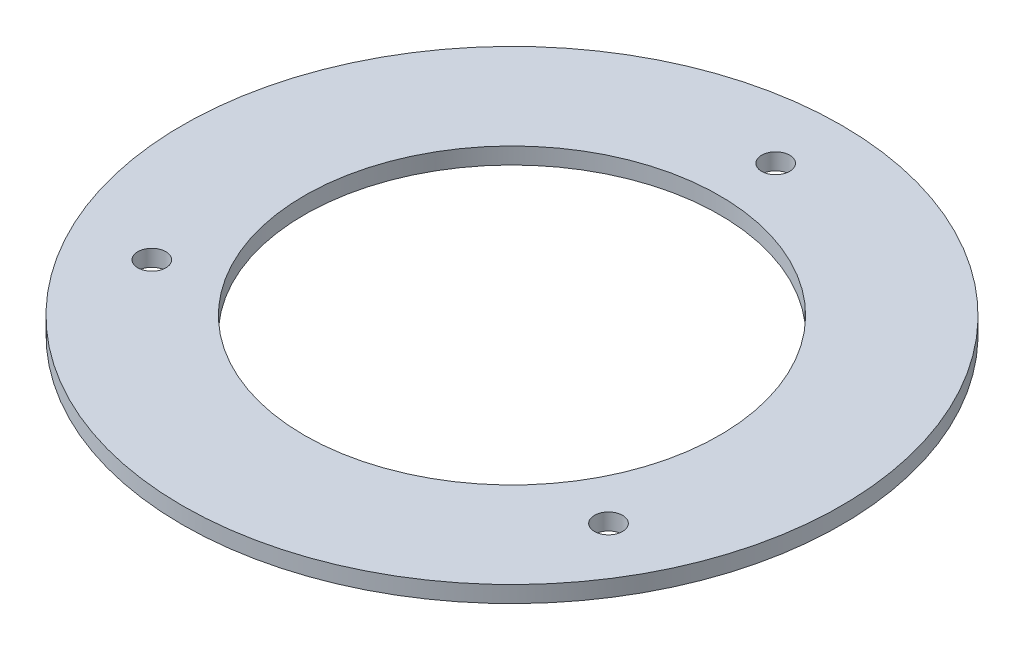
SolidWorks part; units mm, degrees
ref_plane "Front Plane" through (0, 0, 0) normal (0, 0, 1) x (1, 0, 0)
ref_plane "Top Plane" through (0, 0, 0) normal (0, 1, 0) x (1, 0, 0)
ref_plane "Right Plane" through (0, 0, 0) normal (1, 0, 0) x (0, 0, -1)
sketch "Sketch1" plane through (0, 0, 0) normal (0, 1, 0) x (1, 0, 0)
  circle A0 centre (0, 0) radius 63.5
  dimension "D1" = 127
extrude "Boss-Extrude1" add sketch "Sketch1" along normal blind 3.18
sketch "Sketch2" plane through (0, 3.18, 0) normal (0, 1, 0) x (1, 0, 0)
  circle A0 centre (0, 0) radius 40.005
  dimension "D1" = 80.01
extrude "Cut-Extrude1" cut sketch "Sketch2" against normal blind 3.18
ref_axis "Axis2" through (0, 0, 0) along (0, 1, 0)
sketch "Sketch5" plane through (0, 3.18, 0) normal (0, 1, 0) x (1, 0, 0)
  line L0 (0, -64.6358) -> (0, 63.5)
  circle A0 centre (0, 0) radius 63.5 construction
hole_wizard "Hole for #8 300® SC Nuts (SP)1" positions "3DSketch2" profile "Sketch7" hole size "#8-32" standard "PEM® Inch"
sketch3d "3DSketch2"
  line L0 (0, 3.18, 64.6358) -> (0, 3.18, -63.5) construction
  line L1 (0, 0, 0) -> (0, 3.18, 0) construction
  point P0 (0, 3.18, -50.8)
  dimension "D1" = 50.8
sketch "Sketch7" plane through (0, 3.18, -50.8) normal (1, 0, 0) x (0, 0, 1)
  line L0 (0, 0) -> (0, 21.3754)
  line L1 (0, 21.3754) -> (2.7051, 19.75)
  line L2 (2.7051, 19.75) -> (2.7051, 0)
  line L5 (2.7051, 0) -> (0, 0)
  line L10 (0, 21.3754) -> (-2.7051, 19.75) construction
  line L11 (0, -6.35) -> (0, 107.95) construction
  dimension "Hole Dia." = 5.4102
  dimension "Hole Depth" = 19.75
  dimension "Drill Angle" = 118
pattern_circular "CirPattern1" count 3 over 360 about axis through (0, 0, 0) along (0, 1, 0) of "Hole for #8 300® SC Nuts (SP)1"
equation "\"ODia\"= 5in"
equation "\"IDia\"= 3.15in"
equation "\"Thick\"= .125in"
